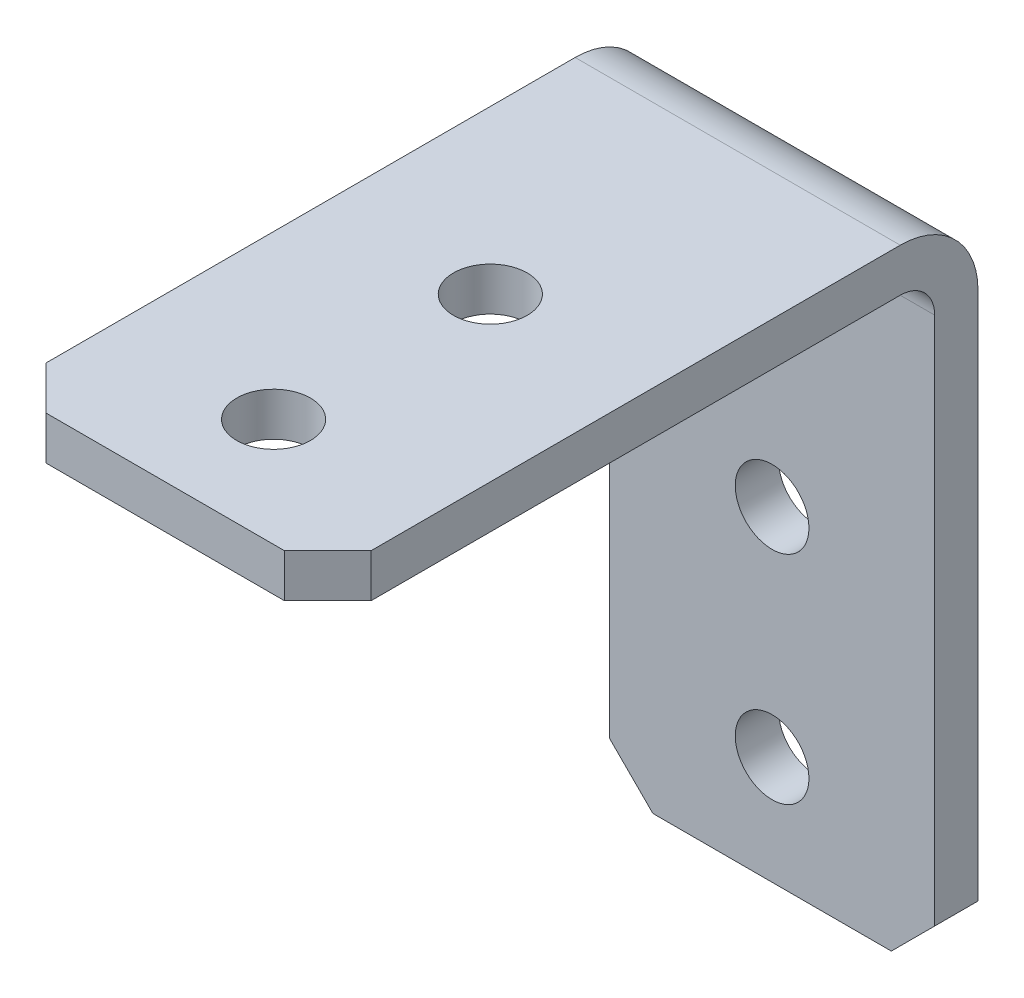
SolidWorks part; units mm, degrees
ref_plane "Front Plane" through (0, 0, 0) normal (0, 0, 1) x (1, 0, 0)
ref_plane "Top Plane" through (0, 0, 0) normal (0, 1, 0) x (1, 0, 0)
ref_plane "Right Plane" through (0, 0, 0) normal (1, 0, 0) x (0, 0, -1)
ref_plane "Plane1" through (-7.5, 0, 0) normal (-1, 0, 0) x (0, -1, 0)
sketch "Sketch1" plane through (-7.5, 0, 0) normal (-1, 0, 0) x (0, -1, 0)
  line L0 (15, -2) -> (15, 28)
  line L1 (15, 28) -> (-15, 28)
  line L2 (-15, 28) -> (-15, -2)
  line L3 (-15, -2) -> (15, -2)
extrude "Boss-Extrude1" add sketch "Sketch1" against normal blind 15
sketch "Sketch2" plane through (7.5, 0, 0) normal (1, 0, 0) x (0, 0, -1)
  line L0 (0, 13) -> (-28, 13)
  line L1 (-28, 13) -> (-28, -15)
  line L2 (-28, -15) -> (0, -15)
  line L3 (0, -15) -> (0, 13)
extrude "Cut-Extrude1" cut sketch "Sketch2" against normal through all
hole_wizard "Ø3.4 (3.4) Diameter Hole1" positions "Sketch4" profile "Sketch3" hole size "Ø3.4" standard "ANSI Metric"
sketch "Sketch4" plane through (0, 0, 0) normal (0, 0, 1) x (1, 0, 0)
  point P0 (0, 0)
  point P1 (0, -10)
sketch "Sketch3" plane through (0, 0, 0) normal (1, 0, 0) x (0, -1, 0)
  line L0 (0, 0) -> (0, 2)
  line L1 (0, 2) -> (1.7, 2)
  line L2 (1.7, 2) -> (1.7, 0)
  line L5 (1.7, 0) -> (0, 0)
  line L11 (0, -6.35) -> (0, 107.95) construction
  dimension "Thru Hole Dia." = 3.4
  dimension "Thru Hole Depth" = 2
hole_wizard "Ø3.4 (3.4) Diameter Hole2" positions "Sketch6" profile "Sketch5" hole size "Ø3.4" standard "ANSI Metric"
sketch "Sketch6" plane through (0, 13, 0) normal (0, -1, 0) x (-1, 0, 0)
  point P0 (0, -13)
  point P1 (0, -23)
sketch "Sketch5" plane through (0, 13, 13) normal (1, 0, 0) x (0, 0, -1)
  line L0 (0, 0) -> (0, 2)
  line L1 (0, 2) -> (1.7, 2)
  line L2 (1.7, 2) -> (1.7, 0)
  line L5 (1.7, 0) -> (0, 0)
  line L11 (0, -6.35) -> (0, 107.95) construction
  dimension "Thru Hole Dia." = 3.4
  dimension "Thru Hole Depth" = 2
chamfer "Chamfer1" distance 2 angle 45 4 edges at (7.5, -15, -1) (-7.5, 14, 28) (7.5, 14, 28) (-7.5, -15, -1)
fillet "Fillet1" radius 1.5875 1 edges at (0, 13, 0) tangent propagation no
fillet "Fillet2" radius 3.5875 1 edges at (0, 15, -2) tangent propagation no
